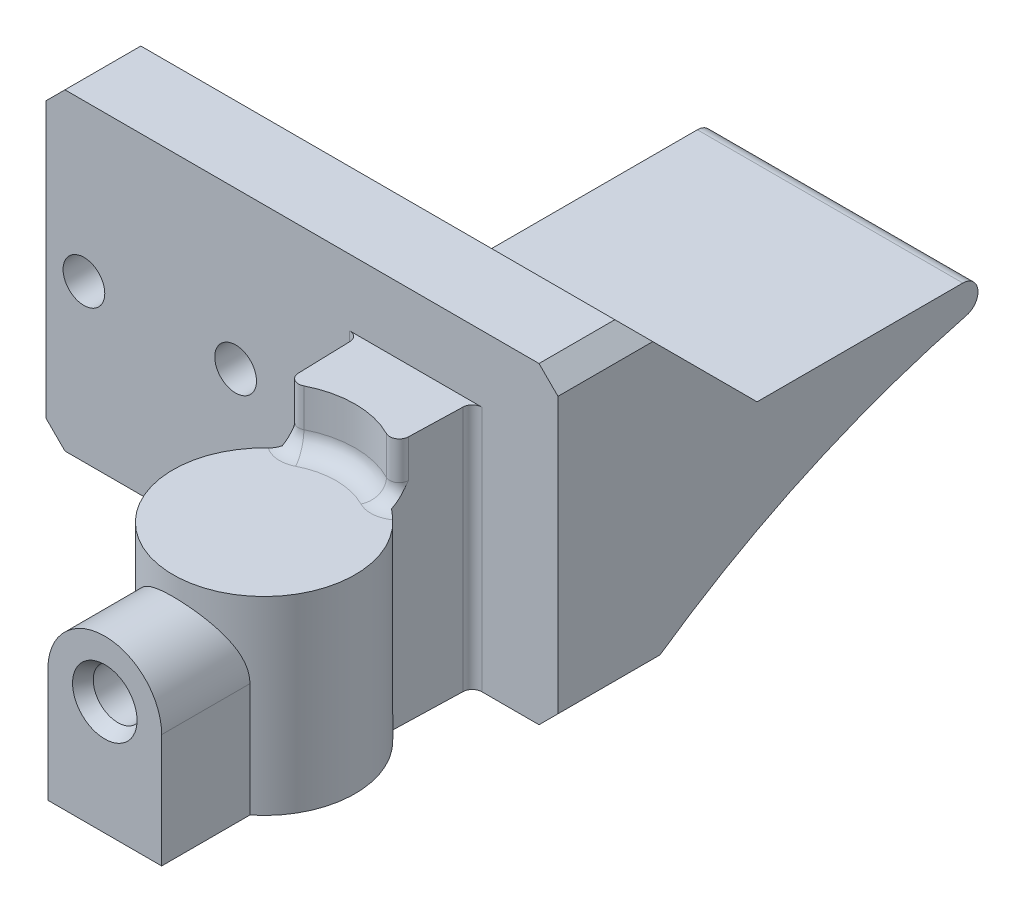
SolidWorks part; units mm, degrees
ref_plane "前视基准面" through (0, 0, 0) normal (0, 0, 1) x (1, 0, 0)
ref_plane "上视基准面" through (0, 0, 0) normal (0, 1, 0) x (1, 0, 0)
ref_plane "右视基准面" through (0, 0, 0) normal (1, 0, 0) x (0, 0, -1)
other "Configuration Table"
sketch "草图1" plane through (0, 0, 0) normal (0, 0, 1) x (1, 0, 0)
  line L0 (-4, 11.4659) -> (-4, -8.5417) construction
  line L5 (9.5, 12.628) -> (9.5, -3.9251) construction
  line L7 (-10, 8.25) -> (17, 8.25)
  line L8 (-10, 8.25) -> (-10, -8.25)
  line L9 (-10, -8.25) -> (17, -8.25)
  line L10 (17, 8.25) -> (17, -8.25)
  line L11 (-10, 8.25) -> (17, -8.25) construction
  line L12 (-10, -8.25) -> (17, 8.25) construction
  point P10 (3.5, 0)
  dimension "D1" = 4
  dimension "D2" = 9.5
  dimension "D3" = 6
  dimension "D4" = 8.25
  dimension "D5" = 16.5
  dimension "D6" = 17
extrude "凸台-拉伸1" add sketch "草图1" along normal blind 4
sketch "草图2" plane through (0, 0, 4) normal (0, 0, 1) x (1, 0, 0)
  line L0 (-4, 200011.4659) -> (-4, -200008.5417) construction
  circle A0 centre (-8, 0) radius 1.1
  circle A1 centre (0, 0) radius 1.1
  dimension "D1" = 2.2
  dimension "D2" = 2.2
  dimension "D3" = 4
  dimension "D4" = 4
extrude "切除-拉伸1" cut sketch "草图2" against normal up to vertex (4 mm away) up to point (-10, -8.25, 0)
sketch "草图3" plane through (0, -8.25, 0) normal (0, -1, 0) x (1, 0, 0)
  line L0 (-10, 4) -> (17, 4) construction
  circle A0 centre (9.5, 12) radius 4.8
  dimension "D1" = 9.6
  dimension "D2" = 8
  dimension "D3" = 9.5
extrude "凸台-拉伸2" add sketch "草图3" against normal blind 10 separate body
sketch "草图4" plane through (0, -8.25, 0) normal (0, -1, 0) x (1, 0, 0)
  line L2 (6.5, 4) -> (12.5, 4)
  line L3 (-10, 4) -> (17, 4) construction
  line L4 (6.62, 8.16) -> (6.5, 4)
  line L5 (12.38, 8.16) -> (12.5, 4)
  circle A1 centre (9.5, 12) radius 4.8
  arc A2 (6.62, 8.16) -> (12.38, 8.16) centre (9.5, 12) ccw
  point P0 (9.5, 12)
  dimension "D3" = 0
extrude "凸台-拉伸3" add sketch "草图4" against normal offset from surface (13 mm away) 3 up to face at (9.5, 1.75, 7.2) offset beyond the face yes
fillet "圆角1" radius 0.5 2 edges at (12.38, 3.25, 8.16) (6.62, 3.25, 8.16)
fillet "圆角2" radius 1 3 edges at (6.8396, 1.75, 7.7072) (12.1604, 1.75, 7.7072) (9.5, 1.75, 7.2)
ref_plane "基准面1" through (0, 0, 20.4) normal (0, 0, 1) x (1, 0, 0)
sketch "草图5" plane through (0, 0, 20.4) normal (0, 0, 1) x (1, 0, 0)
  line L0 (6.5, -8.25) -> (6.5, -2.25)
  line L1 (-10, -8.25) -> (17, -8.25) construction
  line L3 (12.5, -2.25) -> (12.5, -8.25)
  line L4 (6.5, -8.25) -> (12.5, -8.25)
  line L5 (9.5, 200012.628) -> (9.5, -200003.9251) construction
  arc A0 (12.5, -2.25) -> (6.5, -2.25) centre (9.5, -2.25) ccw
  dimension "D4" = 6
  dimension "D1" = 3
  dimension "D2" = 3
  dimension "D3" = 6
extrude "凸台-拉伸4" add sketch "草图5" against normal up to surface (4.653 mm away) up to face at (9.529, -1.5482, 11.0943)
sketch "草图7" plane through (0, 0, 20.4) normal (0, 0, 1) x (1, 0, 0)
  circle A0 centre (9.5, -2.25) radius 1.3
  dimension "D1" = 2.6
extrude "切除-拉伸3" cut sketch "草图7" against normal blind 7
chamfer "倒角1" distance 0.4 angle 60 1 edges at (10.8, -2.25, 20.4) first distance on face at (10.8, -2.25, 20.4)
fillet "圆角3" radius 0.5 2 edges at (12.5, -1.75, 4) (6.5, -1.75, 4)
sketch "草图8" plane through (17, 0, 0) normal (1, 0, 0) x (0, 0, -1)
  line L0 (0, 8.25) -> (0, -8.25) construction
  line L1 (-4, -8.25) -> (0, -8.25) construction
  line L2 (6.5, 1.75) -> (17.3509, 1.75)
  line L3 (0, 8.25) -> (0, -8.25)
  line L4 (0, 8.25) -> (6.5, 1.75)
  arc A0 (17.5501, 0.1752) -> (0, -8.25) centre (30, -48.25) ccw
  arc A1 (17.5501, 0.1752) -> (17.3509, 1.75) centre (17.3509, 0.95) ccw
  dimension "D1" = 30
  dimension "D2" = 40
  dimension "D4" = 0.8
  dimension "D3" = 10
  dimension "D5" = 135
extrude "凸台-拉伸5" add sketch "草图8" against normal blind 14
fillet "圆角4" radius 0.5 1 edges at (3, 0, 0)
chamfer "倒角2" distance 1 angle 45 4 edges at (-10, 8.25, 2) (17, 8.25, 2) (17, -8.25, 2) (-10, -8.25, 2)
